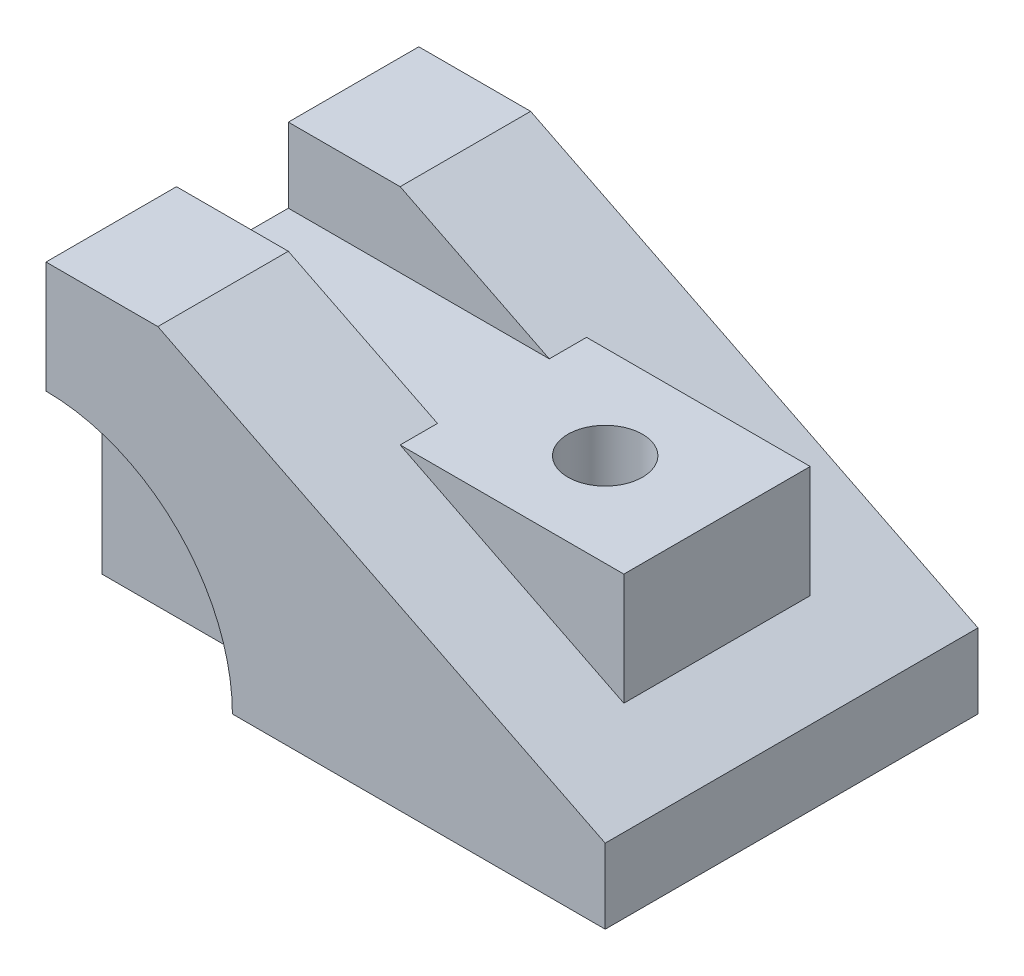
SolidWorks part; units mm, degrees
ref_plane "Front Plane" through (0, 0, 0) normal (0, 0, 1) x (1, 0, 0)
ref_plane "Top Plane" through (0, 0, 0) normal (0, 1, 0) x (1, 0, 0)
ref_plane "Right Plane" through (0, 0, 0) normal (1, 0, 0) x (0, 0, -1)
sketch "Sketch1" plane through (0, 0, 0) normal (0, 0, 1) x (1, 0, 0)
  line L0 (0, 0) -> (150, 0)
  line L1 (150, 0) -> (150, 20)
  line L2 (150, 20) -> (30, 80)
  line L3 (30, 80) -> (0, 80)
  line L4 (0, 80) -> (0, 0)
  dimension "D1" = 150
  dimension "D2" = 20
  dimension "D3" = 80
  dimension "D4" = 30
extrude "Boss-Extrude1" add sketch "Sketch1" against normal blind 50 and the other way blind 50
sketch "Sketch2" plane through (0, 0, 50) normal (0, 0, 1) x (1, 0, 0)
  circle A0 centre (0, 0) radius 50
  dimension "D1" = 100
extrude "Cut-Extrude1" cut sketch "Sketch2" against normal blind 15
sketch "Sketch3" plane through (0, 0, 0) normal (0, 0, 1) x (1, 0, 0)
  line L0 (70, 60) -> (130, 60)
  line L1 (150, 20) -> (30, 80) construction
  line L2 (130, 60) -> (130, 30)
  line L3 (130, 30) -> (70, 60)
  line L4 (150, 0) -> (150, 20) construction
  line L6 (30, 80) -> (0, 80) construction
  point P7 (150, 10)
  dimension "D1" = 20
  dimension "D2" = 30
  dimension "D3" = 20
extrude "Boss-Extrude2" add sketch "Sketch3" along normal blind 25 and the other way blind 25
sketch "Sketch4" plane through (0, 60, 0) normal (0, 1, 0) x (1, 0, 0)
  line L0 (-44, 0) -> (44, 0) construction
  line L2 (130, 25) -> (70, 25) construction
  line L3 (130, 25) -> (130, -25) construction
  circle A0 centre (100, 0) radius 10
  point P4 (0, 0)
  point P6 (0, 0)
  dimension "D1" = 20
  dimension "D2" = 30
  dimension "D3" = 25
extrude "Cut-Extrude2" cut sketch "Sketch4" against normal through all
sketch "Sketch5" plane through (0, 80, 0) normal (0, 1, 0) x (1, 0, 0)
  line L0 (-44, 0) -> (44, 0) construction
  line L1 (-50.1584, 15) -> (83.0747, 15)
  line L2 (-50.1584, 15) -> (-50.1584, -15)
  line L3 (-50.1584, -15) -> (83.0747, -15)
  line L4 (83.0747, 15) -> (83.0747, -15)
  dimension "D1" = 15
  dimension "D2" = 15
extrude "Cut-Extrude3" cut sketch "Sketch5" against normal blind 20
